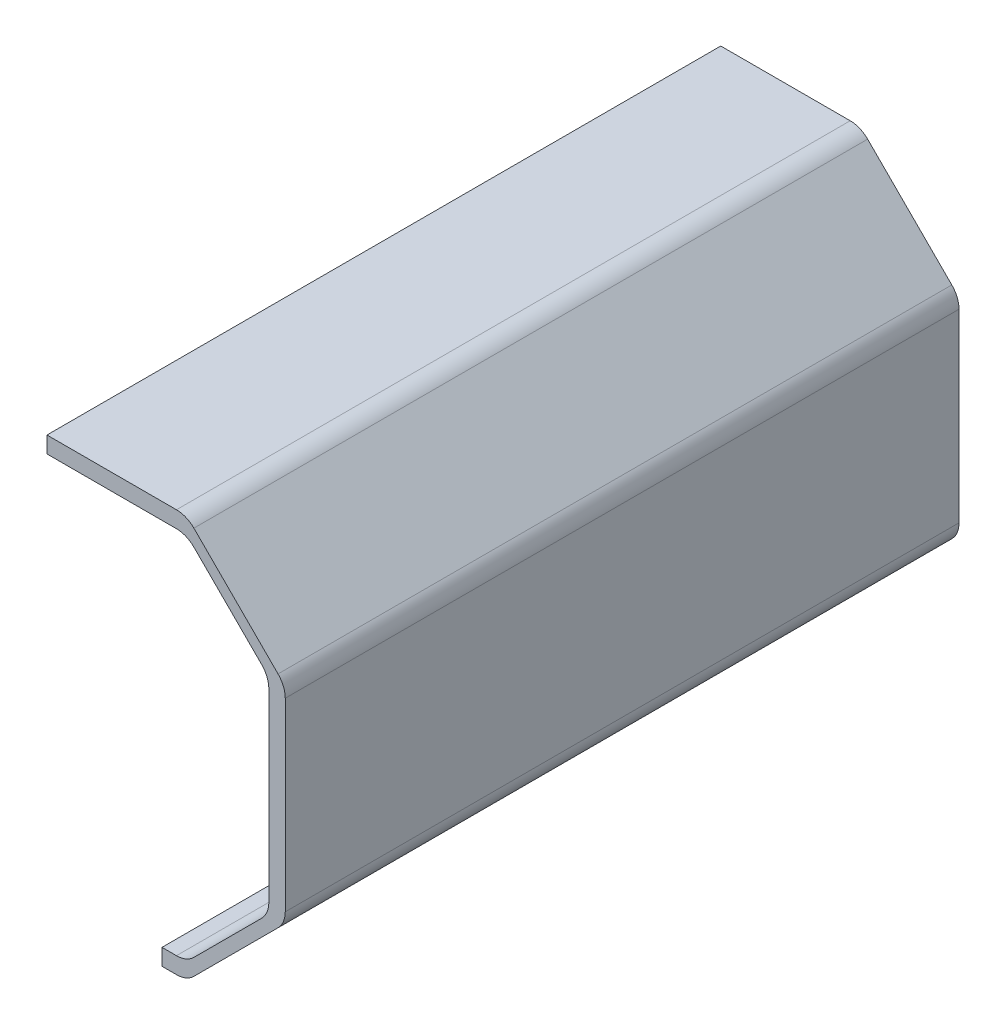
SolidWorks part; units mm, degrees
ref_plane "前视基准面" through (0, 0, 0) normal (0, 0, 1) x (1, 0, 0)
ref_plane "上视基准面" through (0, 0, 0) normal (0, 1, 0) x (1, 0, 0)
ref_plane "右视基准面" through (0, 0, 0) normal (1, 0, 0) x (0, 0, -1)
sketch "草图1" plane through (0, 0, 0) normal (0, 0, 1) x (1, 0, 0)
  line L0 (0, 0) -> (0, 2)
  line L1 (0, 2) -> (3, 2)
  line L5 (-14, 49) -> (3, 49)
  line L7 (0, 0) -> (3, 0)
  line L13 (3, 47) -> (-14, 47)
  line L14 (-14, 49) -> (-14, 47)
  line L15 (3, 2) -> (13, 12)
  line L16 (3, 0) -> (15, 12)
  line L17 (13, 37) -> (13, 12)
  line L18 (15, 12) -> (15, 37)
  line L19 (3, 47) -> (13, 37)
  line L20 (3, 49) -> (15, 37)
extrude "凸台-拉伸1" add sketch "草图1" along normal blind 82
fillet "圆角1" radius 3 8 edges at (3, 0, 41) (15, 12, 41) (15, 37, 41) (3, 49, 41) (3, 2, 41) (13, 12, 41) (13, 37, 41) (3, 47, 41)
